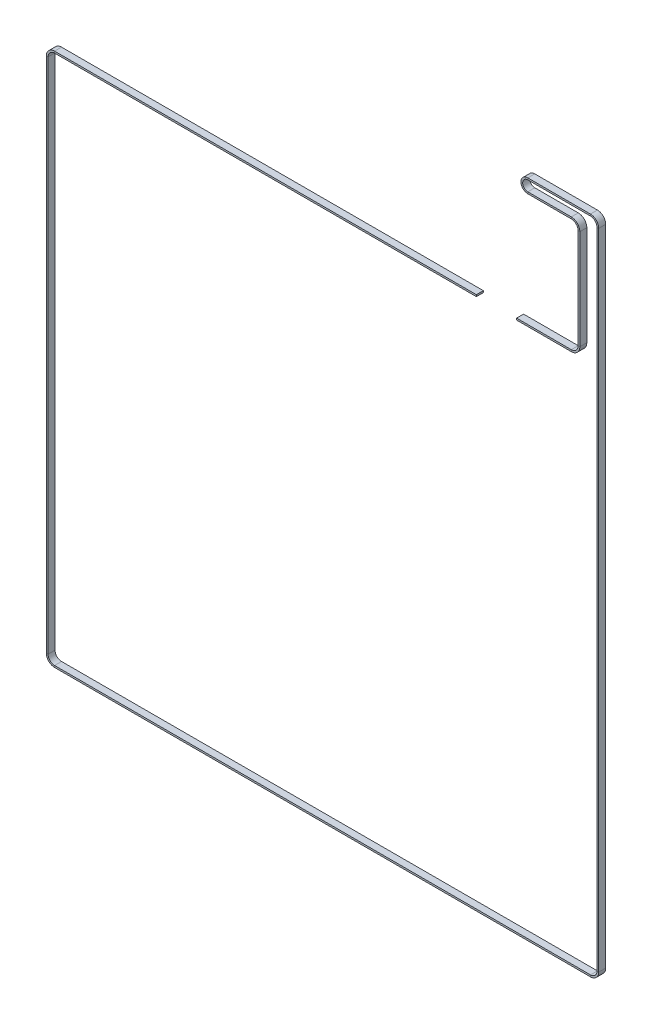
SolidWorks part; units mm, degrees
ref_plane "Front" through (0, 0, 0) normal (0, 0, 1) x (1, 0, 0)
ref_plane "Top" through (0, 0, 0) normal (0, 1, 0) x (1, 0, 0)
ref_plane "Right" through (0, 0, 0) normal (1, 0, 0) x (0, 0, -1)
sketch "Sketch1" plane through (0, 0, 2.2) normal (0, 0, 1) x (1, 0, 0)
  line L0 (377.3122, -142.2854) -> (431.3122, -142.2854)
  line L1 (377.3122, -152.6854) -> (414.8122, -152.6854)
  line L2 (421.4122, -159.2854) -> (421.4122, -245.207)
  line L3 (437.6872, -148.6604) -> (437.6872, -703.9854)
  line L4 (-37.0628, -703.9854) -> (-37.0628, -258.032)
  line L5 (431.3122, -710.3604) -> (-30.6878, -710.3604)
  line L6 (-30.6878, -251.657) -> (332.9622, -251.657)
  line L9 (414.8122, -251.807) -> (367.6622, -251.807)
  line L10 (367.6622, -250.207) -> (367.6622, -255.207) construction
  line L12 (332.9622, -255.207) -> (332.9622, -250.207) construction
  circle A0 centre (414.8122, -159.2854) radius 6.6 construction
  circle A1 centre (431.3122, -148.6604) radius 6.375 construction
  circle A2 centre (377.3122, -147.4854) radius 5.2 construction
  arc A3 (431.3122, -142.2854) -> (437.6872, -148.6604) centre (431.3122, -148.6604) cw
  arc A4 (377.3122, -152.6854) -> (377.3122, -142.2854) centre (377.3122, -147.4854) cw
  arc A5 (414.8122, -152.6854) -> (421.4122, -159.2854) centre (414.8122, -159.2854) cw
  circle A6 centre (-30.6878, -703.9854) radius 6.375 construction
  arc A7 (-30.6878, -710.3604) -> (-37.0628, -703.9854) centre (-30.6878, -703.9854) cw
  circle A8 centre (431.3122, -148.6604) radius 9 construction
  circle A9 centre (414.8122, -159.2854) radius 9 construction
  circle A10 centre (-30.6878, -258.032) radius 6.375 construction
  circle A11 centre (431.3122, -703.9854) radius 6.375 construction
  arc A12 (437.6872, -703.9854) -> (431.3122, -710.3604) centre (431.3122, -703.9854) cw
  arc A13 (-37.0628, -258.032) -> (-30.6878, -251.657) centre (-30.6878, -258.032) cw
  circle A14 centre (414.8122, -245.207) radius 6.6 construction
  arc A15 (421.4122, -245.207) -> (414.8122, -251.807) centre (414.8122, -245.207) cw
  circle A16 centre (414.8122, -245.207) radius 5.9875 construction
  circle A17 centre (-30.6878, -258.032) radius 5.9875 construction
  dimension "D1" = 12.75
ref_plane "Plane1" through (332.9622, -251.657, 2.2) normal (1, 0, 0) x (0, 0, -1)
sketch "Sketch4" plane through (332.9622, -251.657, 2.2) normal (1, 0, 0) x (0, 0, -1)
  line L0 (0, 102.9966) -> (0, -452.3284) construction
  line L1 (3, -0.75) -> (-3, -0.75)
  line L2 (3, -0.75) -> (3, 0.75)
  line L3 (3, 0.75) -> (-3, 0.75)
  line L4 (-3, -0.75) -> (-3, 0.75)
  line L5 (3, -0.75) -> (-3, 0.75) construction
  line L6 (3, 0.75) -> (-3, -0.75) construction
  line L7 (0, 0) -> (0, -12.75) construction
  point P0 (0, 0)
  dimension "D1" = 1.5
  dimension "D2" = 6
sweep "Sweep1" add profiles "Sketch4" path "Sketch1"
